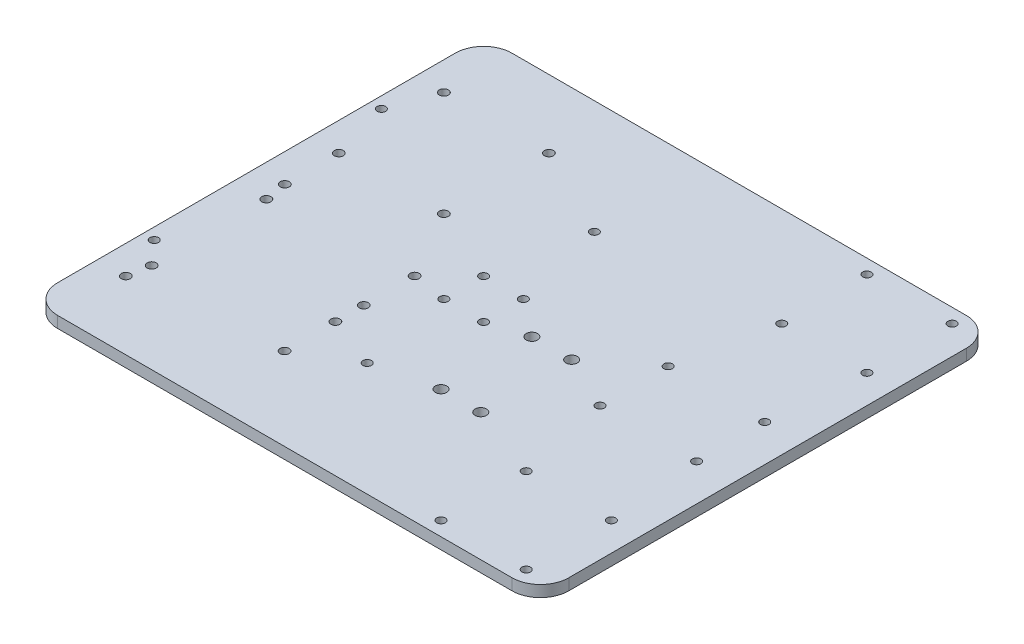
SolidWorks part; units mm, degrees
ref_plane "前视基准面" through (0, 0, 0) normal (0, 0, 1) x (1, 0, 0)
ref_plane "上视基准面" through (0, 0, 0) normal (0, 1, 0) x (1, 0, 0)
ref_plane "右视基准面" through (0, 0, 0) normal (1, 0, 0) x (0, 0, -1)
other "Configuration Table"
sketch "草图1" plane through (0, 0, 0) normal (0, 1, 0) x (1, 0, 0)
  line L1 (-90, -80) -> (90, -80)
  line L2 (-90, -80) -> (-90, 80)
  line L3 (-90, 80) -> (90, 80)
  line L4 (90, -80) -> (90, 80)
  line L5 (-90, -80) -> (90, 80) construction
  line L6 (-90, 80) -> (90, -80) construction
  point P0 (0, 0)
  dimension "D1" = 160
  dimension "D2" = 180
extrude "凸台-拉伸1" add sketch "草图1" along normal blind 4
sketch "草图2" plane through (0, 4, 0) normal (0, 1, 0) x (1, 0, 0)
  line L0 (90, -80) -> (90, 80) construction
  line L1 (66, -25) -> (85, -25) construction
  line L2 (66, -25) -> (66, 25) construction
  line L3 (66, 25) -> (85, 25) construction
  line L4 (85, -25) -> (85, 25) construction
  line L5 (66, -25) -> (85, 25) construction
  line L6 (66, 25) -> (85, -25) construction
  circle A0 centre (66, 25) radius 1.6
  circle A1 centre (66, -25) radius 1.6
  circle A2 centre (85, -25) radius 1.6
  circle A3 centre (85, 25) radius 1.6
  circle A7 centre (80.7, 7) radius 3
  point P0 (75.5, 0)
  dimension "D4" = 3.2
  dimension "D5" = 4.3
  dimension "D7" = 6
  dimension "D1" = 19
  dimension "D2" = 50
  dimension "D3" = 5
  dimension "D6" = 18
sketch "草图4" plane through (0, 4, 0) normal (0, 1, 0) x (1, 0, 0)
  line L0 (90, 80) -> (-90, 80) construction
  line L1 (-80, 56) -> (-43, 56) construction
  line L2 (-80, 56) -> (-80, 19) construction
  line L3 (-80, 19) -> (-43, 19) construction
  line L4 (-43, 56) -> (-43, 19) construction
  line L5 (-90, 80) -> (-90, -80) construction
  circle A0 centre (-80, 56) radius 1.6
  circle A1 centre (-43, 56) radius 1.6
  circle A2 centre (-43, 19) radius 1.6
  circle A3 centre (-80, 19) radius 1.6
  dimension "D4" = 3.2
  dimension "D1" = 37
  dimension "D2" = 24
  dimension "D3" = 10
extrude "切除-拉伸3" cut sketch "草图4" against normal blind 4
sketch "草图5" plane through (0, 4, 0) normal (0, 1, 0) x (1, 0, 0)
  line L0 (-90, -80) -> (90, -80) construction
  line L1 (-80, -56) -> (-29.2, -56) construction
  line L2 (-80, -56) -> (-80, -7.8) construction
  line L3 (-80, -7.8) -> (-29.2, -7.8) construction
  line L4 (-29.2, -56) -> (-29.2, -7.8) construction
  line L5 (-18.0867, -28) -> (49981.9133, -28) construction
  line L6 (-90, 80) -> (-90, -80) construction
  circle A0 centre (-78.7, -7.8) radius 1.6
  circle A1 centre (-29.2, -23) radius 1.6
  circle A2 centre (-29.2, -50.9) radius 1.6
  circle A3 centre (-80, -56) radius 1.6
  circle A4 centre (-29.2, -5.1) radius 1.6
  circle A5 centre (-29.2, -33) radius 1.6
  circle A6 centre (-80, 0) radius 1.6
  circle A7 centre (-78.7, -48.2) radius 1.6
  dimension "D8" = 3.2
  dimension "D1" = 48.2
  dimension "D2" = 50.8
  dimension "D3" = 24
  dimension "D4" = 10
  dimension "D5" = 1.3
  dimension "D6" = 15.2
  dimension "D7" = 27.9
  dimension "D9" = 52
extrude "切除-拉伸4" cut sketch "草图5" against normal blind 4
sketch "草图7" plane through (0, 0, 0) normal (0, -1, 0) x (1, 0, 0)
  line L0 (-90, 80) -> (90, 80) construction
  line L2 (90, 80) -> (90, -80) construction
  circle A0 centre (24, 35) radius 2
  circle A1 centre (10, 35) radius 2
  circle A2 centre (24, 3) radius 2
  circle A3 centre (10, 3) radius 2
  dimension "D2" = 4
  dimension "D5" = 4
  dimension "D1" = 80
  dimension "D3" = 45
  dimension "D6" = 14
  dimension "D7" = 32
extrude "切除-拉伸5" cut sketch "草图7" against normal blind 10
fillet "圆角1" radius 10 4 edges at (90, 2, 80) (90, 2, -80) (-90, 2, -80) (-90, 2, 80)
sketch "草图8" plane through (0, 0, 0) normal (0, -1, 0) x (1, 0, 0)
  line L1 (-17, -7) -> (-3, -7) construction
  line L2 (-17, -7) -> (-17, 7) construction
  line L3 (-17, 7) -> (-3, 7) construction
  line L4 (-3, -7) -> (-3, 7) construction
  line L5 (-17, -7) -> (-3, 7) construction
  line L6 (-17, 7) -> (-3, -7) construction
  circle A0 centre (-17, 7) radius 1.5
  circle A1 centre (-3, 7) radius 1.5
  circle A2 centre (-17, -7) radius 1.5
  circle A3 centre (-3, -7) radius 1.5
  point P0 (-10, 0)
  dimension "D4" = 3
  dimension "D1" = 14
  dimension "D2" = 14
  dimension "D3" = 10
extrude "切除-拉伸6" cut sketch "草图8" against normal blind 10
sketch "草图11" plane through (0, 0, 0) normal (0, -1, 0) x (1, 0, 0)
  line L0 (60, 80) -> (60, -80) construction
  line L1 (-90, 0) -> (90, 0) construction
  line L2 (90, 70) -> (90, -70) construction
  line L3 (-90, -70) -> (-90, 70) construction
  line L4 (80, -80) -> (-80, -80) construction
  line L5 (-80, 80) -> (80, 80) construction
  circle A0 centre (77, 12) radius 1.5
  circle A1 centre (43, 12) radius 1.5
  circle A2 centre (77, -12) radius 1.5
  circle A3 centre (43, -12) radius 1.5
  dimension "D1" = 3
  dimension "D2" = 24
  dimension "D3" = 34
  dimension "D4" = 30
extrude "切除-拉伸8" cut sketch "草图11" against normal blind 4
sketch "草图12" plane through (0, 0, 0) normal (0, -1, 0) x (1, 0, 0)
  line L0 (-90, -70) -> (-90, 70) construction
  line L1 (-11, -40) -> (-86, -40) construction
  line L2 (-11, -40) -> (-11, 40) construction
  line L3 (-11, 40) -> (-86, 40) construction
  line L4 (-86, -40) -> (-86, 40) construction
  line L5 (-11, -40) -> (-86, 40) construction
  line L6 (-11, 40) -> (-86, -40) construction
  circle A0 centre (-86, 40) radius 1.5
  circle A1 centre (-11, 40) radius 1.5
  circle A2 centre (-11, -40) radius 1.5
  circle A3 centre (-86, -40) radius 1.5
  point P0 (-48.5, 0)
  dimension "D4" = 3
  dimension "D1" = 4
  dimension "D2" = 75
  dimension "D3" = 80
extrude "切除-拉伸9" cut sketch "草图12" against normal blind 4
sketch "草图13" plane through (0, 4, 0) normal (0, 1, 0) x (1, 0, 0)
  line L0 (80, 80) -> (-80, 80) construction
  line L1 (90, -70) -> (90, 70) construction
  circle A0 centre (80, 75) radius 1.5
  dimension "D2" = 3
  dimension "D1" = 5
  dimension "D3" = 10
extrude "切除-拉伸10" cut sketch "草图13" against normal blind 10
pattern_linear "阵列(线性)1" count 2 spacing 30 along (-1, 0, 0) count 2 spacing 30 along (0, 0, 1) of "切除-拉伸10"
mirror "镜向1" about plane through (0, 0, 0) normal (0, 0, 1) of "阵列(线性)1"
